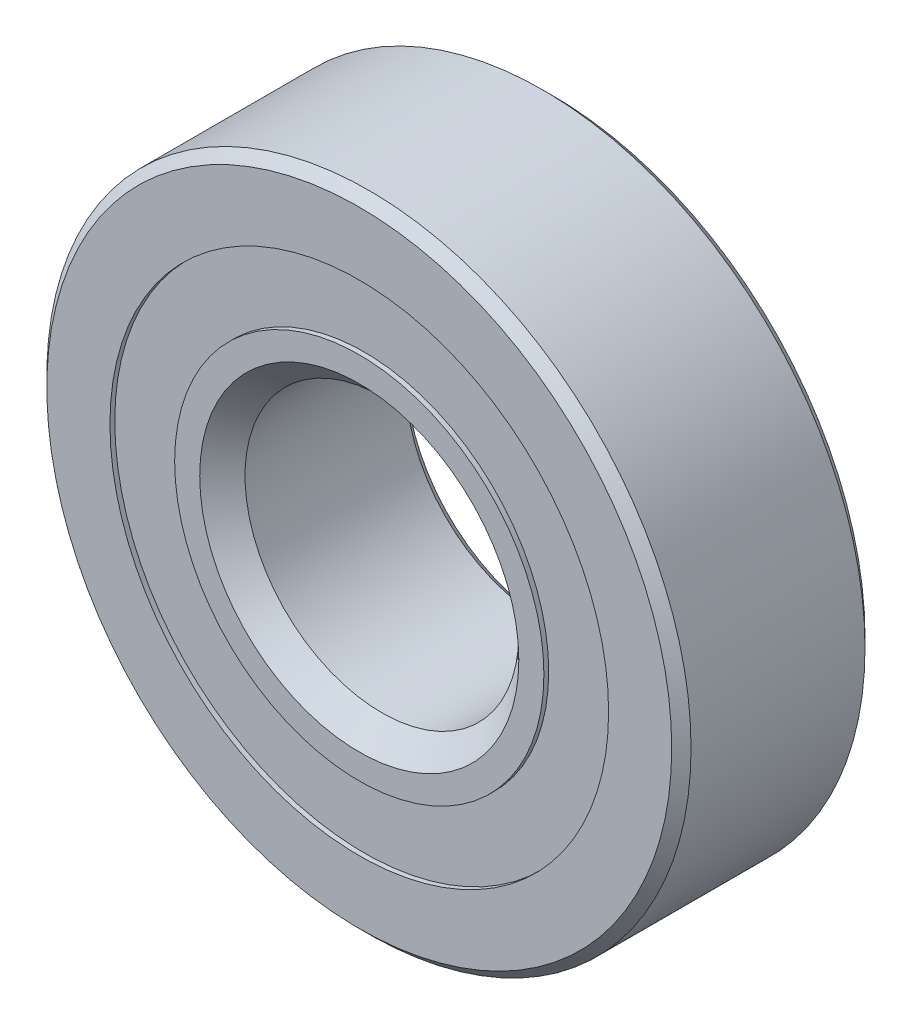
SolidWorks part; units mm, degrees
ref_plane "Front Plane" through (0, 0, 0) normal (0, 0, 1) x (1, 0, 0)
ref_plane "Top Plane" through (0, 0, 0) normal (0, 1, 0) x (1, 0, 0)
ref_plane "Right Plane" through (0, 0, 0) normal (1, 0, 0) x (0, 0, -1)
sketch "Sketch1" plane through (0, 0, 0) normal (1, 0, 0) x (0, 0, -1)
  line L0 (-6, 0) -> (6, 0) construction
  line L1 (0, 20) -> (0, -20) construction
  line L2 (5.4, 20) -> (-5.4, 20)
  line L3 (-5.4, 20) -> (-6, 19.4)
  line L4 (-6, 19.4) -> (-6, 15.4808)
  line L5 (-6, 15.4808) -> (-2.6667, 15.4808)
  line L6 (6, 15.4808) -> (2.6667, 15.4808)
  line L7 (6, 19.4) -> (6, 15.4808)
  line L8 (5.4, 20) -> (6, 19.4)
  line L9 (0, 20) -> (0, 14.25) construction
  line L10 (0, 14.25) -> (0, 8.5) construction
  arc A0 (-2.6667, 15.4808) -> (2.6667, 15.4808) centre (0, 14.25) cw
  point P14 (0, 8.5)
  dimension "Width" = 12
  dimension "OD" = 40
  dimension "D1" = 45
  dimension "D2" = 0.6
  dimension "D3" = 5.3333
  dimension "D4" = 1.2308
revolve "Revolve1" add sketch "Sketch1" angle 360 about L0
sketch "Sketch2" plane through (0, 0, 0) normal (1, 0, 0) x (0, 0, -1)
  line L0 (-5.7, 13.0192) -> (-2.6667, 13.0192)
  line L1 (-6, 19.4) -> (-6, -19.4) construction
  line L2 (-6, 11.4629) -> (-5.7, 11.4629) construction
  line L3 (-5.7, 11.1629) -> (-4.4436, 9.9065)
  line L4 (-4.4436, 9.9065) -> (0, 9.9065)
  line L5 (0, 20) -> (0, -20) construction
  line L6 (0, 9.9065) -> (0, 11.313)
  line L7 (0, 11.313) -> (0, 8.5) construction
  line L8 (-6, 13.0192) -> (-6, 9.9065) construction
  line L9 (-6, 9.9065) -> (-4.4436, 9.9065) construction
  line L10 (-5.7, 13.0192) -> (-5.7, 11.1629)
  line L11 (-5.7, 13.0192) -> (-5.7, 19.7) construction
  line L12 (-5.4, 20) -> (-6, 19.4) construction
  arc A0 (-2.6667, 13.0192) -> (0, 11.313) centre (0, 14.25) ccw
  arc A1 (2.6667, 15.4808) -> (-2.6667, 15.4808) centre (0, 14.25) ccw construction
  circle A2 centre (0, 14.25) radius 2.937 construction
  dimension "D1" = 45
revolve "Revolve2" [suppressed] add sketch "Sketch2" angle 360 about L0
sketch "Sketch3" plane through (0, 0, 0) normal (1, 0, 0) x (0, 0, -1)
  line L0 (-5.7, 11.1629) -> (-4.4436, 9.9065)
  line L1 (-4.4436, 9.9065) -> (0, 9.9065)
  line L2 (0, 9.9065) -> (0, 11.313)
  line L3 (-6, 11.4629) -> (-6, 9.9065)
  line L4 (-6, 13.0192) -> (-6, 9.9065) construction
  line L5 (-6, 9.9065) -> (-4.5935, 8.5)
  line L6 (-4.5935, 8.5) -> (5.4, 8.5)
  line L7 (5.4, 20) -> (5.4, -20) construction
  line L8 (5.4, 8.5) -> (6, 9.1)
  line L9 (6, -19.4) -> (6, 19.4) construction
  line L10 (6, 9.1) -> (6, 13.0192)
  line L11 (6, 13.0192) -> (2.6667, 13.0192)
  line L12 (-6, 11.4629) -> (-5.7, 11.4629)
  line L13 (5.4, 20) -> (6, 19.4) construction
  line L14 (-5.7, 11.4629) -> (-5.7, 11.1629)
  circle A0 centre (0, 14.25) radius 2.937 construction
  arc A1 (2.6667, 13.0192) -> (0, 11.313) centre (0, 14.25) cw
revolve "Revolve3" add sketch "Sketch3" angle 360 about L0
sketch "Sketch4" plane through (0, 0, 0) normal (1, 0, 0) x (0, 0, -1)
  line L0 (-2.937, 14.25) -> (2.937, 14.25)
  circle A1 centre (0, 14.25) radius 2.937 construction
  arc A2 (-2.937, 14.25) -> (2.937, 14.25) centre (0, 14.25) cw
  arc A3 (2.6667, 15.4808) -> (-2.6667, 15.4808) centre (0, 14.25) ccw construction
revolve "Revolve4" add sketch "Sketch4" angle 360 about L0
ref_axis "Axis1" through (0, 0, -6) along (0, 0, 1)
pattern_circular "CirPattern1" count 12 every 30 about axis through (0, 0, -6) along (0, 0, 1) of bodies 104
sketch "Sketch5" plane through (0, 0, 0) normal (1, 0, 0) x (0, 0, -1)
  line L0 (-6, 15.4808) -> (-2.6667, 15.4808) construction
  line L1 (-5.7, 15.4808) -> (-2.937, 15.4808)
  line L2 (-5.7, 15.4808) -> (-5.7, 11.4629)
  line L3 (-5.7, 11.4629) -> (-2.937, 11.4629)
  line L4 (-2.937, 15.4808) -> (-2.937, 11.4629)
  line L6 (-5.4, 20) -> (-6, 19.4) construction
  line L7 (0, 20) -> (0, 8.5) construction
  line L8 (5.7, 11.4629) -> (2.937, 11.4629)
  line L9 (2.937, 15.4808) -> (2.937, 11.4629)
  line L10 (5.7, 15.4808) -> (2.937, 15.4808)
  line L11 (5.7, 15.4808) -> (5.7, 11.4629)
  circle A0 centre (0, 14.25) radius 2.937 construction
  point P10 (-5.7, 19.7)
revolve "Revolve5" add sketch "Sketch5" angle 360 about L0
equation "\"D2@Sketch1\" = \"Width@Sketch1\"*.05"
equation "\"D3@Sketch1\" = \"Width@Sketch1\"/2.25"
equation "\"D4@Sketch1\" = (((\"OD@Sketch1\"-\"Width@Sketch1\")/2)/3.25)/3.5"
equation "\"D2@CirPattern1\" = 360/\"Balls@CirPattern1\""
